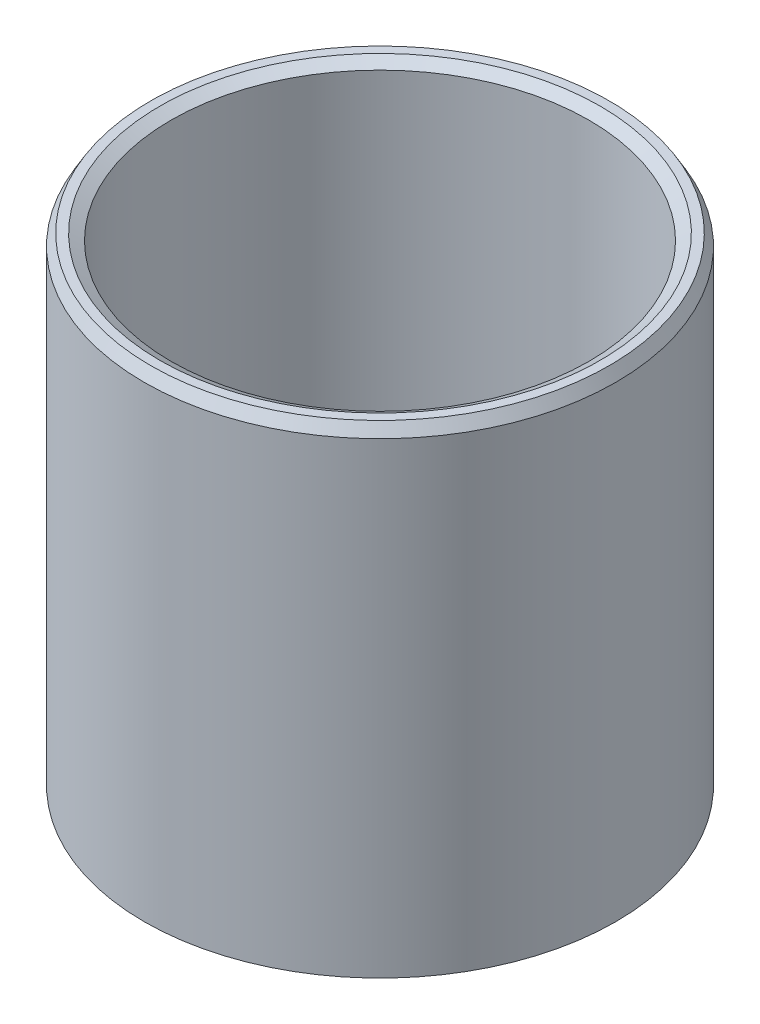
SolidWorks part; units mm, degrees
ref_plane "Front Plane" through (0, 0, 0) normal (0, 0, 1) x (1, 0, 0)
ref_plane "Top Plane" through (0, 0, 0) normal (0, 1, 0) x (1, 0, 0)
ref_plane "Right Plane" through (0, 0, 0) normal (1, 0, 0) x (0, 0, -1)
sketch "Sketch1" plane through (0, 0, 0) normal (0, 1, 0) x (1, 0, 0)
  circle A0 centre (0, 0) radius 42.5
  dimension "SLEEVE_OD" = 85
extrude "Boss-Extrude1" add sketch "Sketch1" along normal blind 87.3823
sketch "Sketch2" plane through (0, 0, 0) normal (0, 1, 0) x (1, 0, 0)
  circle A0 centre (0, 0) radius 37.6621
  dimension "BORE_D" = 75.3243
extrude "Cut-Extrude1" cut sketch "Sketch2" along normal through all
chamfer "Chamfer1" distance 2.0253 angle 30 4 edges at (0, 87.3823, 37.6621) (0, 0, 37.6621) (0, 0, 42.5) (0, 87.3823, 42.5) first distance on face at (0, 87.3823, 37.6621) first distance on face at (0, 0, 37.6621) first distance on face at (0, 87.3823, 42.5)
